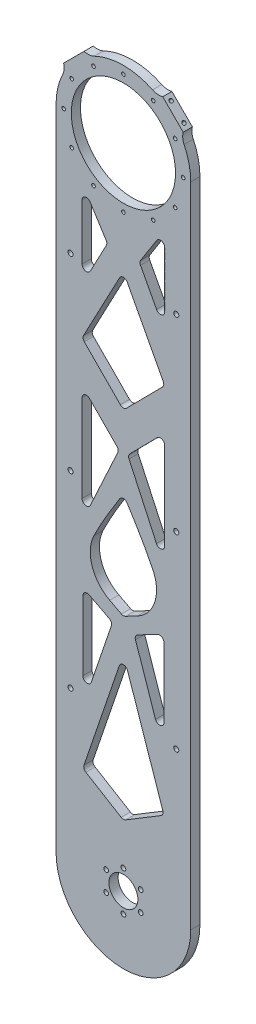
SolidWorks part; units mm, degrees
material "1060 Alloy"
ref_plane "Front Plane" through (0, 0, 0) normal (0, 0, 1) x (1, 0, 0)
ref_plane "Top Plane" through (0, 0, 0) normal (0, 1, 0) x (1, 0, 0)
ref_plane "Right Plane" through (0, 0, 0) normal (1, 0, 0) x (0, 0, -1)
sketch "Sketch2" plane through (0, 0, 0) normal (0, 0, 1) x (1, 0, 0)
  line L0 (0, 0) -> (0, 500) construction
  line L1 (-46.5, 0) -> (-46.5, 500)
  line L2 (46.5, 0) -> (46.5, 500)
  arc A0 (-46.5, 0) -> (46.5, 0) centre (0, 0) ccw
  arc A1 (46.5, 500) -> (-46.5, 500) centre (0, 500) ccw
  circle A2 centre (0, 500) radius 37.25 construction
  circle A3 centre (0, 0) radius 10
  circle A4 centre (0, 13.75) radius 1.65
  circle A5 centre (0, 0) radius 13.75 construction
  circle A6 centre (11.9078, 6.875) radius 1.65
  circle A7 centre (11.9078, -6.875) radius 1.65
  circle A8 centre (0, -13.75) radius 1.65
  circle A9 centre (-11.9078, -6.875) radius 1.65
  circle A10 centre (-11.9078, 6.875) radius 1.65
  point P3 (0, 250)
  point P27 (0, 0)
  dimension "D2" = 74.5
  dimension "D4" = 20
  dimension "D5" = 3.3
  dimension "D6" = 27.5
  dimension "D3" = 46.5
  dimension "D1" = 500
  dimension "D7" = 6
extrude "Boss-Extrude1" add sketch "Sketch2" along normal blind 6.35
sketch "Sketch4" plane through (0, 0, 6.35) normal (0, 0, 1) x (1, 0, 0)
  line L0 (0, 500) -> (0, 999.1647) construction
  line L29 (46.5, 500) -> (-46.5, 500) construction
  line L31 (28.0053, 59.376) -> (0, 42.4117)
  line L32 (0, 141.6934) -> (28.0053, 59.376)
  line L33 (-28.0053, 59.376) -> (0, 141.6934)
  line L34 (0, 42.4117) -> (-28.0053, 59.376)
  line L35 (-7.5, 156.9059) -> (-28.0053, 96.6336)
  line L36 (-28.0053, 167.5829) -> (-7.5, 156.9059)
  line L37 (-28.0053, 96.6336) -> (-28.0053, 167.5829)
  line L38 (28.0053, 167.5829) -> (7.5, 156.9059)
  line L39 (28.0053, 96.6336) -> (28.0053, 167.5829)
  line L40 (7.5, 156.9059) -> (28.0053, 96.6336)
  line L41 (0, 164.2751) -> (28.5505, 179.1412)
  line L42 (0, 164.2751) -> (-28.5505, 179.1412)
  line L43 (28.5505, 259.5868) -> (3, 314.9383)
  line L44 (28.5505, 340.7931) -> (28.5505, 259.5868)
  line L45 (3, 314.9383) -> (28.5505, 340.7931)
  line L46 (-3, 314.9383) -> (-28.5505, 340.7931)
  line L47 (-28.5505, 259.5868) -> (-3, 314.9383)
  line L48 (-28.5505, 340.7931) -> (-28.5505, 259.5868)
  line L49 (0, 423.1428) -> (-28.5505, 369.2462)
  line L50 (-28.5505, 369.2462) -> (0, 340.3557)
  line L51 (0, 340.3557) -> (28.5505, 369.2462)
  line L52 (0, 423.1428) -> (28.5505, 369.2462)
  line L53 (-28.5505, 462.0952) -> (-28.5505, 401.2902)
  line L54 (-11, 434.4215) -> (-28.5505, 462.0952)
  line L55 (-28.5505, 401.2902) -> (-11, 434.4215)
  line L56 (28.5505, 401.2902) -> (11, 434.4215)
  line L57 (28.5505, 462.0952) -> (28.5505, 401.2902)
  line L58 (11, 434.4215) -> (28.5505, 462.0952)
  arc A0 (46.5, 500) -> (-46.5, 500) centre (0, 500) ccw construction
  arc A1 (46.5, 500) -> (-46.5, 500) centre (0, 500) ccw construction
  spline S2 degree 3 poles (28.5505, 179.1412) (45.3203, 216.9857) (19.4301, 259.7903) (0, 290.0258) knots 0 0 0 0 1 1 1 1
  spline S3 degree 3 poles (-28.5505, 179.1412) (-45.3203, 216.9857) (-19.4301, 259.7903) (0, 290.0258) knots 0 0 0 0 1 1 1 1
extrude "Cut-Extrude1" cut sketch "Sketch4" against normal blind 10
fillet "Fillet3" radius 3 30 edges at (-11, 434.4215, 3.175) (-28.5505, 401.2902, 3.175) (28.5505, 401.2902, 3.175) (11, 434.4215, 3.175) (28.5505, 462.0952, 3.175) (-28.5505, 462.0952, 3.175) (0, 423.1428, 3.175) (-28.5505, 369.2462, 3.175) (28.5505, 369.2462, 3.175) (0, 340.3557, 3.175) (28.5505, 340.7931, 3.175) (-28.5505, 340.7931, 3.175) (-3, 314.9383, 3.175) (3, 314.9383, 3.175) (28.5505, 259.5868, 3.175) (-28.5505, 259.5868, 3.175) (28.5505, 179.1412, 3.175) (0, 290.0258, 3.175) (-28.5505, 179.1412, 3.175) (0, 164.2751, 3.175) (-28.0053, 96.6336, 3.175) (28.0053, 96.6336, 3.175) (7.5, 156.9059, 3.175) (-28.0053, 167.5829, 3.175) (28.0053, 167.5829, 3.175) (0, 141.6934, 3.175) (28.0053, 59.376, 3.175) (-28.0053, 59.376, 3.175) (0, 42.4117, 3.175) (-7.5, 156.9059, 3.175)
sketch "Sketch5" plane through (0, 0, 6.35) normal (0, 0, 1) x (1, 0, 0)
  line L0 (0, -46.5) -> (108.8395, -46.5) construction
  line L1 (46.5, 100) -> (-46.5, 100) construction
  line L2 (46.5, 0) -> (46.5, 500) construction
  line L3 (-46.5, 500) -> (-46.5, 0) construction
  line L4 (-46.5, 106.35) -> (46.5, 106.35) construction
  line L5 (36.5, 106.35) -> (36.5, 100) construction
  line L6 (0, 106.35) -> (0, 100) construction
  line L7 (-46.5, 256.35) -> (46.5, 256.35) construction
  line L8 (-46.5, 181.35) -> (46.5, 181.35) construction
  line L9 (-46.5, 337.7) -> (46.5, 337.7) construction
  arc A1 (-46.5, 0) -> (46.5, 0) centre (0, 0) ccw construction
  circle A2 centre (36.5, 103.175) radius 1.75
  circle A3 centre (-36.5, 103.175) radius 1.75
  circle A4 centre (36.5, 259.525) radius 1.75
  circle A5 centre (-36.5, 259.525) radius 1.75
  circle A6 centre (36.5, 415.875) radius 1.75
  circle A7 centre (-36.5, 415.875) radius 1.75
  point P18 (36.5, 103.175)
  dimension "D2" = 3.5
  dimension "D1" = 146.5
  dimension "D3" = 10
  dimension "D4" = 6.35
  dimension "D5" = 150
  dimension "D6" = 81.35
  dimension "D7" = 81.35
extrude "Cut-Extrude2" cut sketch "Sketch5" against normal through all
sketch "Sketch6" plane through (0, 0, 6.35) normal (0, 0, 1) x (1, 0, 0)
  circle A0 centre (0, 500) radius 26.5
  arc A1 (46.5, 500) -> (-46.5, 500) centre (0, 500) ccw construction
  arc A2 (46.5, 500) -> (-46.5, 500) centre (0, 500) ccw construction
  dimension "D1" = 20
extrude "Cut-Extrude3" cut sketch "Sketch6" against normal blind 10
sketch "Sketch7" plane through (0, 0, 6.35) normal (0, 0, 1) x (1, 0, 0)
  line L1 (40.0163, 523.6842) -> (44.1104, 529.9682) construction
  line L2 (23.6842, 540.0163) -> (29.9682, 544.1104) construction
  line L3 (44.1104, 529.9682) -> (29.9682, 544.1104)
  line L4 (0, 500) -> (37.0393, 537.0393) construction
  line L5 (0, 500) -> (0, 546.5) construction
  arc A0 (46.5, 500) -> (-46.5, 500) centre (0, 500) ccw construction
  arc A1 (29.9682, 544.1104) -> (16.4747, 543.4837) centre (22.4977, 559.381) cw
  arc A2 (44.1104, 529.9682) -> (43.4837, 516.4747) centre (59.381, 522.4977) ccw
  arc A3 (16.4747, 543.4837) -> (43.4837, 516.4747) centre (0, 500) cw
  dimension "D3" = 17
  dimension "D5" = 17
  dimension "D1" = 20
  dimension "D2" = 7.5
  dimension "D4" = 8
  dimension "D6" = 8
  dimension "D7" = 45
extrude "Boss-Extrude2" add sketch "Sketch7" against normal up to surface (6.35 mm away) up to face at (26.5, 500, 0)
sketch "Sketch8" plane through (287.0393, 287.0393, 0) normal (0.7071, 0.7071, 0) x (0, 0, -1)
  line L0 (0, 363.5534) -> (-6.35, 363.5534) construction
  line L1 (0, 343.5534) -> (-6.35, 343.5534) construction
  line L2 (-6.35, 343.5534) -> (-6.35, 363.5534) construction
  point P0 (-3.175, 359.5534)
  point P1 (-3.175, 347.5534)
  dimension "D1" = 4
  dimension "D2" = 4
  dimension "D3" = 3.175
hole_wizard "Tap Drill for M3x0.5 Tap1" positions "Sketch8" profile "Sketch9" hole size "M3x0.5" standard "ANSI Metric"
sketch "Sketch9" plane through (32.7967, 541.282, 3.175) normal (0, 0, 1) x (-0.7071, 0.7071, 0)
  line L0 (0, 0) -> (0, 5.7511)
  line L1 (0, 5.7511) -> (1.25, 5)
  line L2 (1.25, 5) -> (1.25, 0)
  line L5 (1.25, 0) -> (0, 0)
  line L10 (0, 5.7511) -> (-1.25, 5) construction
  line L11 (0, -6.35) -> (0, 107.95) construction
  dimension "Hole Dia." = 2.5
  dimension "Hole Depth" = 5
  dimension "Drill Angle" = 118
pattern_circular "CirPattern2" count 2 every 90 about axis through (0, 500, -3.65) along (0, 0, 1) of "Boss-Extrude2", "Tap Drill for M3x0.5 Tap1"
sketch "Sketch10" plane through (0, 0, 6.35) normal (0, 0, 1) x (1, 0, 0)
  line L0 (-43.4837, 516.4747) -> (-63.4837, 516.4747)
  line L1 (43.4837, 516.4747) -> (63.4837, 516.4747)
  arc A0 (43.4837, 516.4747) -> (-43.4837, 516.4747) centre (0, 500) ccw
  arc A1 (46.5, 500) -> (43.4837, 516.4747) centre (0, 500) ccw construction
  arc A2 (-63.4837, 516.4747) -> (63.4837, 516.4747) centre (0, 500) cw
  dimension "D1" = 19.0866
  dimension "D2" = 20
extrude "Cut-Extrude4" cut sketch "Sketch10" against normal through all
sketch "Sketch11" plane through (0, 0, 6.35) normal (0, 0, 1) x (1, 0, 0)
  circle A0 centre (0, 500) radius 36
  circle A1 centre (0, 500) radius 26.5 construction
  dimension "D1" = 72
extrude "Cut-Extrude5" cut sketch "Sketch11" against normal through all
sketch "Sketch12" plane through (0, 0, 6.35) normal (0, 0, 1) x (1, 0, 0)
  line L0 (0, 536) -> (0, 546.5) construction
  circle A0 centre (0, 500) radius 41.25 construction
  circle A1 centre (0, 500) radius 36 construction
  arc A2 (46.5, 500) -> (-46.5, 500) centre (0, 500) ccw construction
  circle A3 centre (0, 541.25) radius 1.25
  circle A4 centre (20.625, 535.7235) radius 1.25
  circle A5 centre (35.7235, 520.625) radius 1.25
  circle A6 centre (41.25, 500) radius 1.25
  circle A7 centre (35.7235, 479.375) radius 1.25
  circle A8 centre (20.625, 464.2765) radius 1.25
  circle A9 centre (0, 458.75) radius 1.25
  circle A10 centre (-20.625, 464.2765) radius 1.25
  circle A11 centre (-35.7235, 479.375) radius 1.25
  circle A12 centre (-41.25, 500) radius 1.25
  circle A13 centre (-35.7235, 520.625) radius 1.25
  circle A14 centre (-20.625, 535.7235) radius 1.25
  point P9 (0, 541.25)
  point P36 (0, 500)
  dimension "D1" = 2.5
  dimension "D2" = 12
extrude "Cut-Extrude6" cut sketch "Sketch12" against normal through all both and the other way through all
sketch "Sketch13" plane through (0, 0, 0) normal (0, 0, -1) x (-1, 0, 0)
  line L0 (28.984, 180.1429) -> (28.984, 234.0954) construction
  line L1 (-28.984, 180.1429) -> (-28.984, 234.0954) construction
  line L2 (46.5, 234.0954) -> (-46.5, 234.0954)
  line L3 (46.5, 500) -> (46.5, 0) construction
  line L4 (-46.5, 0) -> (-46.5, 500) construction
  line L5 (46.5, 180.1429) -> (-46.5, 180.1429)
  line L6 (-46.5, 234.0954) -> (-46.5, 180.1429)
  line L7 (46.5, 234.0954) -> (46.5, 180.1429)
  spline S0 degree 3 poles (2.5314, 286.068) (21.3968, 256.4039) (44.1773, 216.1126) (28.984, 180.1429) knots 0.042883 0.042883 0.042883 0.042883 0.991187 0.991187 0.991187 0.991187 construction
  spline S1 degree 3 poles (-28.984, 180.1429) (-44.1773, 216.1126) (-21.3968, 256.4039) (-2.5314, 286.068) knots 0.008813 0.008813 0.008813 0.008813 0.957117 0.957117 0.957117 0.957117 construction
extrude "Cut-Extrude7" cut sketch "Sketch13" against normal through all
move or copy body "Body-Move/Copy1" bodies to move or copy 111 copy no translate (0, -52.7177, 0) parameters "D1"=0, "D2"=52.7177, "D3"=0
sketch "Sketch14" plane through (0, 180.1429, 0) normal (0, 1, 0) x (1, 0, 0)
  line L0 (-28.984, 0) -> (-46.5, 0) construction
  line L1 (-46.5, 0) -> (-46.5, -6.35) construction
  line L2 (-46.5, -6.35) -> (-28.984, -6.35) construction
  line L3 (-28.984, -6.35) -> (-28.984, 0) construction
  line L4 (28.984, -6.35) -> (46.5, -6.35) construction
  line L5 (46.5, -6.35) -> (46.5, 0) construction
  line L6 (46.5, 0) -> (28.984, 0) construction
  line L7 (28.984, 0) -> (28.984, -6.35) construction
  line L8 (-28.984, 0) -> (-46.5, 0)
  line L9 (-46.5, 0) -> (-46.5, -6.35)
  line L10 (-46.5, -6.35) -> (-28.984, -6.35)
  line L11 (-28.984, -6.35) -> (-28.984, 0)
  line L12 (28.984, -6.35) -> (46.5, -6.35)
  line L13 (46.5, -6.35) -> (46.5, 0)
  line L14 (46.5, 0) -> (28.984, 0)
  line L15 (28.984, 0) -> (28.984, -6.35)
extrude "Boss-Extrude3" add sketch "Sketch14" along normal up to surface (1.2348 mm away) up to face at (37.742, 181.3777, 3.175)
sketch "Sketch15" plane through (0, 0, 0) normal (0, 0, -1) x (-1, 0, 0)
  line L0 (-1.3855, 164.9966) -> (-27.606, 178.6494) construction
  line L1 (28.984, 181.3777) -> (28.984, 180.1429)
  line L2 (-28.984, 181.3777) -> (-28.984, 180.1429) construction
  line L3 (-9.4381, 169.1895) -> (-27.606, 178.6494)
  line L4 (-28.984, 181.3777) -> (-28.984, 180.1429)
  line L5 (0, 493.7823) -> (0, -46.5) construction
  line L6 (9.4381, 169.1895) -> (27.606, 178.6494)
  arc A0 (-20.3344, 202.3794) -> (-9.4381, 169.1895) centre (2.1078, 191.3636) ccw
  arc A1 (-28.984, 180.1429) -> (-27.606, 178.6494) centre (-26.2204, 181.3103) ccw construction
  arc A2 (-28.984, 180.1429) -> (-27.606, 178.6494) centre (-26.2204, 181.3103) ccw
  arc A3 (46.5, 447.2823) -> (-46.5, 447.2823) centre (0, 447.2823) ccw construction
  arc A4 (-46.5, 0) -> (46.5, 0) centre (0, 0) ccw construction
  arc A5 (28.984, 180.1429) -> (27.606, 178.6494) centre (26.2204, 181.3103) cw
  arc A6 (20.3344, 202.3794) -> (9.4381, 169.1895) centre (-2.1078, 191.3636) cw
  spline S0 degree 3 poles (1953.7087, 263.1445) (-2215.7642, -533.3919) (2154.4506, 1213.369) (-1849.5555, -532.5784) knots -2.670349 -2.670349 -2.670349 -2.670349 4.338748 4.338748 4.338748 4.338748 only from (-28.984, 181.3777) to (-2.5314, 233.3503) construction
  spline S1 degree 3 poles (28.984, 181.3777) (26.6659, 188.5284) (23.6788, 195.566) (20.3344, 202.3794) knots 0.47109 0.47109 0.47109 0.47109 0.656208 0.656208 0.656208 0.656208
  spline S2 degree 3 poles (-28.984, 181.3777) (-26.6659, 188.5284) (-23.6788, 195.566) (-20.3344, 202.3794) knots 0.47109 0.47109 0.47109 0.47109 0.656208 0.656208 0.656208 0.656208
  dimension "D1" = 25
  dimension "D2" = 540.2823
extrude "Boss-Extrude4" add sketch "Sketch15" against normal up to surface (6.35 mm away) up to face at (2.6453, 187.7844, 6.35)
sketch "Sketch16" plane through (0, 0, 0) normal (0, 0, -1) x (-1, 0, 0)
  line L0 (36.5, 103.175) -> (36.5, 363.1573) construction
  line L1 (-36.5, 103.175) -> (-36.5, 363.1573) construction
  circle A0 centre (-36.5, 363.1573) radius 1.75 construction
  circle A1 centre (36.5, 363.1573) radius 1.75 construction
  circle A2 centre (-36.5, 103.175) radius 1.75 construction
  circle A3 centre (36.5, 103.175) radius 1.75 construction
  circle A4 centre (-36.5, 363.1573) radius 1.75 construction
  circle A5 centre (36.5, 363.1573) radius 1.75 construction
  circle A6 centre (-36.5, 103.175) radius 1.75 construction
  circle A7 centre (36.5, 103.175) radius 1.75 construction
  circle A8 centre (36.5, 233.1662) radius 1.75
  circle A9 centre (-36.5, 233.1662) radius 1.75
  point P16 (36.5, 233.1662)
  point P18 (36.5, 233.1662)
extrude "Cut-Extrude8" cut sketch "Sketch16" against normal through all
sketch "Sketch17" plane through (0, 0, 0) normal (0, 0, -1) x (-1, 0, 0)
  circle A0 centre (36.5, 206.8073) radius 1.75 construction
  circle A1 centre (-36.5, 206.8073) radius 1.75 construction
  circle A2 centre (36.5, 206.8073) radius 1.75
  circle A3 centre (-36.5, 206.8073) radius 1.75
extrude "Boss-Extrude5" add sketch "Sketch17" against normal up to surface (6.35 mm away) up to face at (-34.75, 233.1662, 6.35)
sketch "Sketch18" plane through (0, 0, 0) normal (0, 0, -1) x (-1, 0, 0)
  line L0 (0, 447.2823) -> (0, 493.7823) construction
  line L1 (0, 447.2823) -> (32.8805, 480.1628) construction
  line L2 (-10, 492.6943) -> (-10, 495.6943) construction
  line L3 (25.0401, 486.4645) -> (27.1614, 488.5858)
  line L4 (27.1614, 488.5858) -> (41.3035, 474.4437)
  line L5 (41.3035, 474.4437) -> (39.1822, 472.3224)
  line L6 (25.0401, 486.4645) -> (39.1822, 472.3224)
  line L7 (-10, 495.6943) -> (10, 495.6943) construction
  line L8 (10, 495.6943) -> (10, 492.6943) construction
  line L9 (-10, 492.6943) -> (10, 492.6943) construction
  line L10 (-39.1822, 472.3224) -> (-41.3035, 474.4437)
  line L11 (-41.3035, 474.4437) -> (-27.1614, 488.5858)
  line L12 (-27.1614, 488.5858) -> (-25.0401, 486.4645)
  line L13 (-39.1822, 472.3224) -> (-25.0401, 486.4645)
  arc A0 (46.5, 447.2823) -> (-46.5, 447.2823) centre (0, 447.2823) ccw construction
  point P11 (32.1111, 479.3934)
  point P13 (0, 492.6943)
  dimension "D1" = 45
  dimension "D2" = 20
  dimension "D3" = 3
  dimension "D4" = 3
extrude "Boss-Extrude6" add sketch "Sketch18" against normal up to surface (6.35 mm away) up to face at (-34.75, 233.1662, 6.35)
sketch "Sketch20" plane through (-257.8736, 257.8736, 0) normal (-0.7071, 0.7071, 0) x (0, 0, 1)
  line L0 (6.35, 316.2764) -> (0, 316.2764) construction
  line L1 (6.35, 306.2764) -> (6.35, 326.2764) construction
  line L2 (0, 306.2764) -> (0, 326.2764) construction
  point P0 (3.175, 322.5264)
  point P9 (3.175, 316.2764)
  point P10 (3.175, 310.0264)
  dimension "D1" = 12.5
hole_wizard "M3x0.5 Tapped Hole1" positions "Sketch20" profile "Sketch21" tap size "M3x0.5" standard "ANSI Metric"
sketch "Sketch21" plane through (-29.813, 485.9342, 3.175) normal (0, 0, 1) x (-0.7071, -0.7071, 0)
  line L0 (0, 0) -> (0, 8.2511)
  line L1 (0, 8.2511) -> (1.25, 7.5)
  line L2 (1.25, 7.5) -> (1.25, 0)
  line L5 (1.25, 0) -> (0, 0)
  line L10 (0, 8.2511) -> (-1.25, 7.5) construction
  line L11 (0, -6.35) -> (0, 107.95) construction
  dimension "Tap Drill Dia." = 2.5
  dimension "Tap Drill Depth" = 7.5
  dimension "Drill Angle" = 118
cosmetic thread "Hole Thread1" parameters "D1"=6, "D2"=3
cosmetic thread "Hole Thread2" parameters "D1"=6, "D2"=3
pattern_circular "CirPattern3" count 2 over 90 about axis through (0, 447.2823, 0) along (0, 0, 1) of "M3x0.5 Tapped Hole1" reverse direction yes
cosmetic thread "Hole Thread5" parameters "D1"=6, "D2"=3
cosmetic thread "Hole Thread6" parameters "D1"=6, "D2"=3
cosmetic thread "Hole Thread7" parameters "D1"=6, "D2"=3
cosmetic thread "Hole Thread8" parameters "D1"=6, "D2"=3
fillet "Fillet4" radius 10 4 edges at (-39.1822, 472.3224, 3.175) (-25.0401, 486.4645, 3.175) (39.1822, 472.3224, 3.175) (25.0401, 486.4645, 3.175)
equation "\"L1L\"=500"
equation "\"L1Thick\"=6.35"
equation "\"D1@Sketch2\"=\"L1L\""
equation "\"Harm-Drive-Outer\"=74.5"
equation "\"D2@Sketch2\"=\"Harm-Drive-Outer\""
equation "\"D1@Boss-Extrude1\"=\"L1Thick\""
